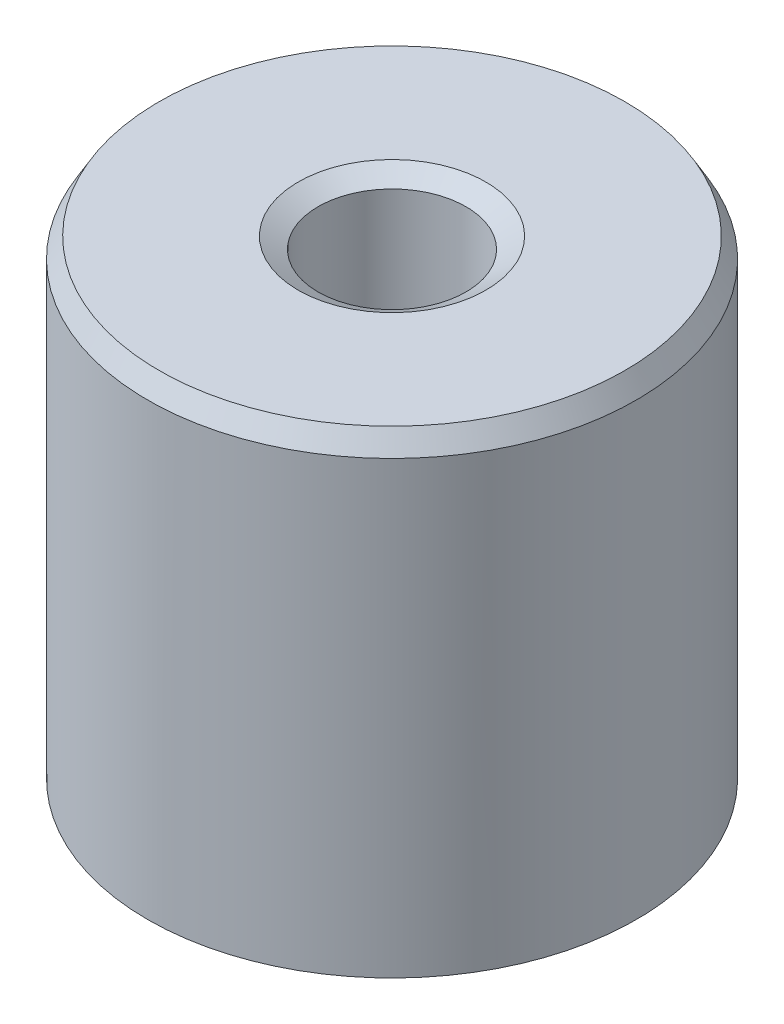
SolidWorks part; units mm, degrees
ref_plane "Front Plane" through (0, 0, 0) normal (0, 0, 1) x (1, 0, 0)
ref_plane "Top Plane" through (0, 0, 0) normal (0, 1, 0) x (1, 0, 0)
ref_plane "Right Plane" through (0, 0, 0) normal (1, 0, 0) x (0, 0, -1)
sketch "Sketch1" plane through (0, 0, 0) normal (0, 1, 0) x (1, 0, 0)
  circle A0 centre (0, 0) radius 7.5
  dimension "SLEEVE_OD" = 15
extrude "Boss-Extrude1" add sketch "Sketch1" along normal blind 14.7706
sketch "Sketch2" plane through (0, 0, 0) normal (0, 1, 0) x (1, 0, 0)
  circle A0 centre (0, 0) radius 2.2697
  dimension "BORE_D" = 4.5395
extrude "Cut-Extrude1" cut sketch "Sketch2" along normal through all
chamfer "Chamfer1" distance 0.6092 angle 30 4 edges at (0, 14.7706, 2.2697) (0, 0, 2.2697) (0, 0, 7.5) (0, 14.7706, 7.5) first distance on face at (0, 14.7706, 2.2697) first distance on face at (0, 0, 2.2697) first distance on face at (0, 14.7706, 7.5)
